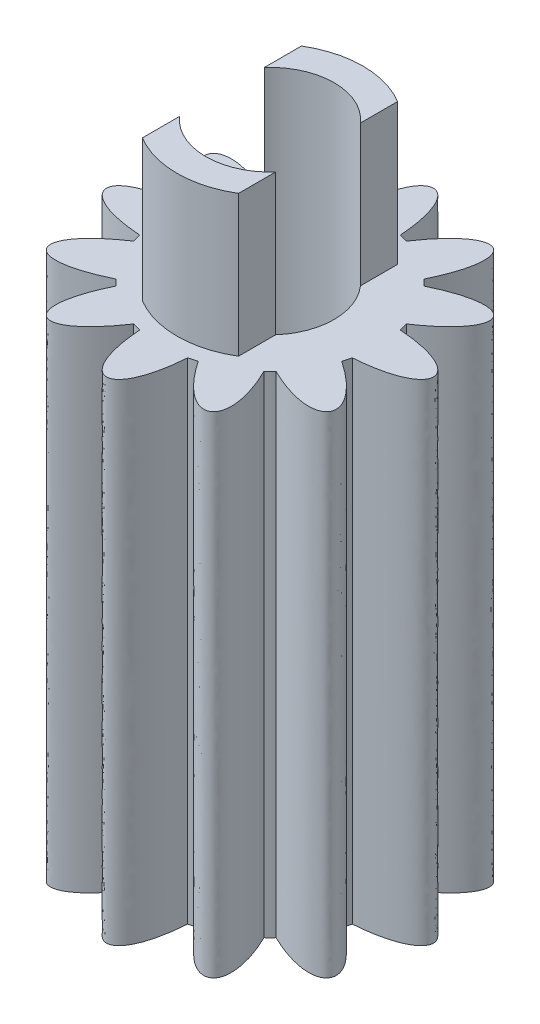
SolidWorks part; units mm, degrees
ref_plane "Front Plane" through (0, 0, 0) normal (0, 0, 1) x (1, 0, 0)
ref_plane "Top Plane" through (0, 0, 0) normal (0, 1, 0) x (1, 0, 0)
ref_plane "Right Plane" through (0, 0, 0) normal (1, 0, 0) x (0, 0, -1)
sketch "Sketch1" plane through (0, 0, 0) normal (0, 1, 0) x (1, 0, 0)
  line L0 (0, 0.0596) -> (0, 50000.0596) construction
  line L1 (0.75, -3.3162) -> (-0.75, -3.3162) construction
  line L2 (0.75, -3.3162) -> (0.75, 3.3162) construction
  line L3 (0.75, 3.3162) -> (-0.75, 3.3162) construction
  line L4 (-0.75, -3.3162) -> (-0.75, 3.3162) construction
  line L5 (0.75, -3.3162) -> (-0.75, 3.3162) construction
  line L6 (0.75, 3.3162) -> (-0.75, -3.3162) construction
  line L7 (0, 0) -> (0.75, 3.3162) construction
  circle A0 centre (0, 0) radius 3.4
  circle A1 centre (0, 0) radius 5.1 construction
  spline S0 degree 3 poles (-0.75, 3.3162) (-0.5833, 5.6946) (0.5833, 5.6946) (0.75, 3.3162) knots 0 0 0 0 1 1 1 1
  spline S1 degree 3 poles (1.0086, 3.247) (2.3421, 5.2233) (3.3525, 4.64) (2.3076, 2.497) knots 0 0 0 0 1 1 1 1
  spline S2 degree 3 poles (2.497, 2.3076) (4.64, 3.3525) (5.2233, 2.3421) (3.247, 1.0086) knots 0 0 0 0 1 1 1 1
  spline S3 degree 3 poles (3.3162, 0.75) (5.6946, 0.5833) (5.6946, -0.5833) (3.3162, -0.75) knots 0 0 0 0 1 1 1 1
  spline S4 degree 3 poles (3.247, -1.0086) (5.2233, -2.3421) (4.64, -3.3525) (2.497, -2.3076) knots 0 0 0 0 1 1 1 1
  spline S5 degree 3 poles (2.3076, -2.497) (3.3525, -4.64) (2.3421, -5.2233) (1.0086, -3.247) knots 0 0 0 0 1 1 1 1
  spline S6 degree 3 poles (0.75, -3.3162) (0.5833, -5.6946) (-0.5833, -5.6946) (-0.75, -3.3162) knots 0 0 0 0 1 1 1 1
  spline S7 degree 3 poles (-1.0086, -3.247) (-2.3421, -5.2233) (-3.3525, -4.64) (-2.3076, -2.497) knots 0 0 0 0 1 1 1 1
  spline S8 degree 3 poles (-2.497, -2.3076) (-4.64, -3.3525) (-5.2233, -2.3421) (-3.247, -1.0086) knots 0 0 0 0 1 1 1 1
  spline S9 degree 3 poles (-3.3162, -0.75) (-5.6946, -0.5833) (-5.6946, 0.5833) (-3.3162, 0.75) knots 0 0 0 0 1 1 1 1
  spline S10 degree 3 poles (-3.247, 1.0086) (-5.2233, 2.3421) (-4.64, 3.3525) (-2.497, 2.3076) knots 0 0 0 0 1 1 1 1
  spline S11 degree 3 poles (-2.3076, 2.497) (-3.3525, 4.64) (-2.3421, 5.2233) (-1.0086, 3.247) knots 0 0 0 0 1 1 1 1
  dimension "D1" = 6.8
  dimension "D2" = 10.2
  dimension "D3" = 1.5
  dimension "D4" = 3.4
extrude "Boss-Extrude1" add sketch "Sketch1" along normal blind 15.3 contours A0 | S9 A0 | S8 A0 | S7 A0 | S6 A0 | S5 A0 | S4 A0 | S3 A0 | S2 A0 | S1 A0 | S10 A0 | S11 A0 | S0 A0 region at (0, 0, 0) region at (4.0967, 0, 0) region at (3.5479, 0, -2.0484) region at (3.5479, 0, 2.0484) region at (2.0484, 0, -3.5479) region at (2.0484, 0, 3.5479) region at (0, 0, -4.0967) region at (0, 0, 4.0967) region at (-2.0484, 0, -3.5479) region at (-2.0484, 0, 3.5479) region at (-3.5479, 0, -2.0484) region at (-3.5479, 0, 2.0484) region at (-4.0967, 0, 0)
sketch "Sketch4" plane through (0, 15.3, 0) normal (0, 1, 0) x (1, 0, 0)
  circle A0 centre (0, 0) radius 2.9
  dimension "D1" = 5.8
extrude "Boss-Extrude2" add sketch "Sketch4" along normal blind 4.4
sketch "Sketch2" plane through (0, 0, 0) normal (0, -1, 0) x (1, 0, 0)
  circle A0 centre (0, 0) radius 2
  dimension "D1" = 4
extrude "Cut-Extrude2" cut sketch "Sketch2" against normal blind 19.7
sketch "Sketch5" plane through (0, 15.3, 0) normal (0, 1, 0) x (1, 0, 0)
  line L1 (1.5, -6) -> (-1.5, -6) construction
  line L2 (1.5, -6) -> (1.5, 6) construction
  line L3 (1.5, 6) -> (-1.5, 6) construction
  line L4 (-1.5, -6) -> (-1.5, 6) construction
  line L5 (1.5, -6) -> (-1.5, 6) construction
  line L6 (1.5, 6) -> (-1.5, -6) construction
  line L7 (1.5, 6) -> (3.5, 6)
  line L8 (1.5, 6) -> (1.5, -6)
  line L9 (1.5, -6) -> (3.5, -6)
  line L10 (3.5, 6) -> (3.5, -6)
  line L11 (-1.5, 6) -> (-3.5, 6)
  line L12 (-1.5, 6) -> (-1.5, -6)
  line L13 (-1.5, -6) -> (-3.5, -6)
  line L14 (-3.5, 6) -> (-3.5, -6)
  point P0 (0, 0)
  dimension "D1" = 3
  dimension "D2" = 12
  dimension "D3" = 2
extrude "Cut-Extrude3" cut sketch "Sketch5" along normal up to surface (4.4 mm away) up to face at (0, 19.7, -2)
